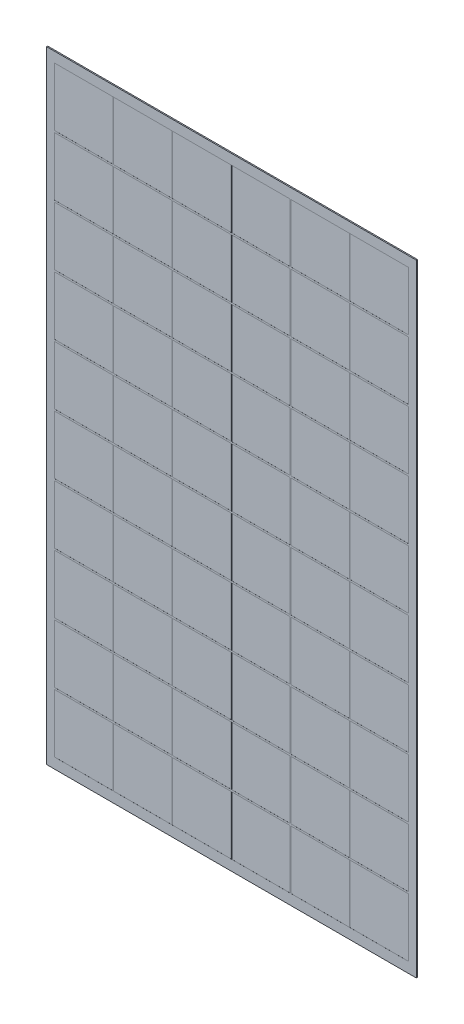
SolidWorks part; units mm, degrees
material "Glass"
ref_plane "Front Plane" through (0, 0, 0) normal (0, 0, 1) x (1, 0, 0)
ref_plane "Top Plane" through (0, 0, 0) normal (0, 1, 0) x (1, 0, 0)
ref_plane "Right Plane" through (0, 0, 0) normal (1, 0, 0) x (0, 0, -1)
sketch "Sketch1" plane through (0, 0, 0) normal (0, 0, 1) x (1, 0, 0)
  line L1 (0, 0) -> (980, 0)
  line L2 (0, 0) -> (0, 1648)
  line L3 (0, 1648) -> (980, 1648)
  line L4 (980, 0) -> (980, 1648)
  dimension "D1" = 980
  dimension "D2" = 1648
extrude "Boss-Extrude1" add sketch "Sketch1" along normal blind 3
sketch "Sketch2" plane through (0, 0, 3) normal (0, 0, 1) x (1, 0, 0)
  line L0 (0, 1648) -> (0, 0) construction
  line L1 (21, 1621) -> (176, 1621)
  line L2 (21, 1621) -> (21, 1466)
  line L3 (21, 1466) -> (176, 1466)
  line L4 (176, 1621) -> (176, 1466)
  line L5 (980, 1648) -> (0, 1648) construction
  line L6 (177.6, 1621) -> (177.6, 1466)
  line L7 (177.6, 1621) -> (332.6, 1621)
  line L8 (332.6, 1621) -> (332.6, 1466)
  line L9 (177.6, 1466) -> (332.6, 1466)
  line L10 (334.2, 1621) -> (334.2, 1466)
  line L11 (334.2, 1621) -> (489.2, 1621)
  line L12 (489.2, 1621) -> (489.2, 1466)
  line L13 (334.2, 1466) -> (489.2, 1466)
  line L14 (490.8, 1621) -> (490.8, 1466)
  line L15 (490.8, 1621) -> (645.8, 1621)
  line L16 (645.8, 1621) -> (645.8, 1466)
  line L17 (490.8, 1466) -> (645.8, 1466)
  line L18 (647.4, 1621) -> (647.4, 1466)
  line L19 (647.4, 1621) -> (802.4, 1621)
  line L20 (802.4, 1621) -> (802.4, 1466)
  line L21 (647.4, 1466) -> (802.4, 1466)
  line L22 (804, 1621) -> (804, 1466)
  line L23 (804, 1621) -> (959, 1621)
  line L24 (959, 1621) -> (959, 1466)
  line L25 (804, 1466) -> (959, 1466)
  line L27 (21, 1461.2) -> (21, 1306.2)
  line L28 (21, 1461.2) -> (176, 1461.2)
  line L29 (176, 1461.2) -> (176, 1306.2)
  line L30 (21, 1306.2) -> (176, 1306.2)
  line L31 (177.6, 1461.2) -> (177.6, 1306.2)
  line L32 (177.6, 1306.2) -> (332.6, 1306.2)
  line L33 (332.6, 1461.2) -> (332.6, 1306.2)
  line L34 (177.6, 1461.2) -> (332.6, 1461.2)
  line L35 (334.2, 1461.2) -> (334.2, 1306.2)
  line L36 (334.2, 1306.2) -> (489.2, 1306.2)
  line L37 (489.2, 1461.2) -> (489.2, 1306.2)
  line L38 (334.2, 1461.2) -> (489.2, 1461.2)
  line L39 (490.8, 1461.2) -> (490.8, 1306.2)
  line L40 (490.8, 1306.2) -> (645.8, 1306.2)
  line L41 (645.8, 1461.2) -> (645.8, 1306.2)
  line L42 (490.8, 1461.2) -> (645.8, 1461.2)
  line L43 (647.4, 1461.2) -> (647.4, 1306.2)
  line L44 (647.4, 1306.2) -> (802.4, 1306.2)
  line L45 (802.4, 1461.2) -> (802.4, 1306.2)
  line L46 (647.4, 1461.2) -> (802.4, 1461.2)
  line L47 (804, 1461.2) -> (804, 1306.2)
  line L48 (804, 1306.2) -> (959, 1306.2)
  line L49 (959, 1461.2) -> (959, 1306.2)
  line L50 (804, 1461.2) -> (959, 1461.2)
  line L51 (21, 1301.4) -> (21, 1146.4)
  line L52 (21, 1301.4) -> (176, 1301.4)
  line L53 (176, 1301.4) -> (176, 1146.4)
  line L54 (21, 1146.4) -> (176, 1146.4)
  line L55 (177.6, 1301.4) -> (177.6, 1146.4)
  line L56 (177.6, 1146.4) -> (332.6, 1146.4)
  line L57 (332.6, 1301.4) -> (332.6, 1146.4)
  line L58 (177.6, 1301.4) -> (332.6, 1301.4)
  line L59 (334.2, 1301.4) -> (334.2, 1146.4)
  line L60 (334.2, 1146.4) -> (489.2, 1146.4)
  line L61 (489.2, 1301.4) -> (489.2, 1146.4)
  line L62 (334.2, 1301.4) -> (489.2, 1301.4)
  line L63 (490.8, 1301.4) -> (490.8, 1146.4)
  line L64 (490.8, 1146.4) -> (645.8, 1146.4)
  line L65 (645.8, 1301.4) -> (645.8, 1146.4)
  line L66 (490.8, 1301.4) -> (645.8, 1301.4)
  line L67 (647.4, 1301.4) -> (647.4, 1146.4)
  line L68 (647.4, 1146.4) -> (802.4, 1146.4)
  line L69 (802.4, 1301.4) -> (802.4, 1146.4)
  line L70 (647.4, 1301.4) -> (802.4, 1301.4)
  line L71 (804, 1301.4) -> (804, 1146.4)
  line L72 (804, 1146.4) -> (959, 1146.4)
  line L73 (959, 1301.4) -> (959, 1146.4)
  line L74 (804, 1301.4) -> (959, 1301.4)
  line L75 (21, 1141.6) -> (21, 986.6)
  line L76 (21, 1141.6) -> (176, 1141.6)
  line L77 (176, 1141.6) -> (176, 986.6)
  line L78 (21, 986.6) -> (176, 986.6)
  line L79 (177.6, 1141.6) -> (177.6, 986.6)
  line L80 (177.6, 986.6) -> (332.6, 986.6)
  line L81 (332.6, 1141.6) -> (332.6, 986.6)
  line L82 (177.6, 1141.6) -> (332.6, 1141.6)
  line L83 (334.2, 1141.6) -> (334.2, 986.6)
  line L84 (334.2, 986.6) -> (489.2, 986.6)
  line L85 (489.2, 1141.6) -> (489.2, 986.6)
  line L86 (334.2, 1141.6) -> (489.2, 1141.6)
  line L87 (490.8, 1141.6) -> (490.8, 986.6)
  line L88 (490.8, 986.6) -> (645.8, 986.6)
  line L89 (645.8, 1141.6) -> (645.8, 986.6)
  line L90 (490.8, 1141.6) -> (645.8, 1141.6)
  line L91 (647.4, 1141.6) -> (647.4, 986.6)
  line L92 (647.4, 986.6) -> (802.4, 986.6)
  line L93 (802.4, 1141.6) -> (802.4, 986.6)
  line L94 (647.4, 1141.6) -> (802.4, 1141.6)
  line L95 (804, 1141.6) -> (804, 986.6)
  line L96 (804, 986.6) -> (959, 986.6)
  line L97 (959, 1141.6) -> (959, 986.6)
  line L98 (804, 1141.6) -> (959, 1141.6)
  line L99 (21, 981.8) -> (21, 826.8)
  line L100 (21, 981.8) -> (176, 981.8)
  line L101 (176, 981.8) -> (176, 826.8)
  line L102 (21, 826.8) -> (176, 826.8)
  line L103 (177.6, 981.8) -> (177.6, 826.8)
  line L104 (177.6, 826.8) -> (332.6, 826.8)
  line L105 (332.6, 981.8) -> (332.6, 826.8)
  line L106 (177.6, 981.8) -> (332.6, 981.8)
  line L107 (334.2, 981.8) -> (334.2, 826.8)
  line L108 (334.2, 826.8) -> (489.2, 826.8)
  line L109 (489.2, 981.8) -> (489.2, 826.8)
  line L110 (334.2, 981.8) -> (489.2, 981.8)
  line L111 (490.8, 981.8) -> (490.8, 826.8)
  line L112 (490.8, 826.8) -> (645.8, 826.8)
  line L113 (645.8, 981.8) -> (645.8, 826.8)
  line L114 (490.8, 981.8) -> (645.8, 981.8)
  line L115 (647.4, 981.8) -> (647.4, 826.8)
  line L116 (647.4, 826.8) -> (802.4, 826.8)
  line L117 (802.4, 981.8) -> (802.4, 826.8)
  line L118 (647.4, 981.8) -> (802.4, 981.8)
  line L119 (804, 981.8) -> (804, 826.8)
  line L120 (804, 826.8) -> (959, 826.8)
  line L121 (959, 981.8) -> (959, 826.8)
  line L122 (804, 981.8) -> (959, 981.8)
  line L123 (21, 822) -> (21, 667)
  line L124 (21, 822) -> (176, 822)
  line L125 (176, 822) -> (176, 667)
  line L126 (21, 667) -> (176, 667)
  line L127 (177.6, 822) -> (177.6, 667)
  line L128 (177.6, 667) -> (332.6, 667)
  line L129 (332.6, 822) -> (332.6, 667)
  line L130 (177.6, 822) -> (332.6, 822)
  line L131 (334.2, 822) -> (334.2, 667)
  line L132 (334.2, 667) -> (489.2, 667)
  line L133 (489.2, 822) -> (489.2, 667)
  line L134 (334.2, 822) -> (489.2, 822)
  line L135 (490.8, 822) -> (490.8, 667)
  line L136 (490.8, 667) -> (645.8, 667)
  line L137 (645.8, 822) -> (645.8, 667)
  line L138 (490.8, 822) -> (645.8, 822)
  line L139 (647.4, 822) -> (647.4, 667)
  line L140 (647.4, 667) -> (802.4, 667)
  line L141 (802.4, 822) -> (802.4, 667)
  line L142 (647.4, 822) -> (802.4, 822)
  line L143 (804, 822) -> (804, 667)
  line L144 (804, 667) -> (959, 667)
  line L145 (959, 822) -> (959, 667)
  line L146 (804, 822) -> (959, 822)
  line L147 (21, 662.2) -> (21, 507.2)
  line L148 (21, 662.2) -> (176, 662.2)
  line L149 (176, 662.2) -> (176, 507.2)
  line L150 (21, 507.2) -> (176, 507.2)
  line L151 (177.6, 662.2) -> (177.6, 507.2)
  line L152 (177.6, 507.2) -> (332.6, 507.2)
  line L153 (332.6, 662.2) -> (332.6, 507.2)
  line L154 (177.6, 662.2) -> (332.6, 662.2)
  line L155 (334.2, 662.2) -> (334.2, 507.2)
  line L156 (334.2, 507.2) -> (489.2, 507.2)
  line L157 (489.2, 662.2) -> (489.2, 507.2)
  line L158 (334.2, 662.2) -> (489.2, 662.2)
  line L159 (490.8, 662.2) -> (490.8, 507.2)
  line L160 (490.8, 507.2) -> (645.8, 507.2)
  line L161 (645.8, 662.2) -> (645.8, 507.2)
  line L162 (490.8, 662.2) -> (645.8, 662.2)
  line L163 (647.4, 662.2) -> (647.4, 507.2)
  line L164 (647.4, 507.2) -> (802.4, 507.2)
  line L165 (802.4, 662.2) -> (802.4, 507.2)
  line L166 (647.4, 662.2) -> (802.4, 662.2)
  line L167 (804, 662.2) -> (804, 507.2)
  line L168 (804, 507.2) -> (959, 507.2)
  line L169 (959, 662.2) -> (959, 507.2)
  line L170 (804, 662.2) -> (959, 662.2)
  line L171 (21, 502.4) -> (21, 347.4)
  line L172 (21, 502.4) -> (176, 502.4)
  line L173 (176, 502.4) -> (176, 347.4)
  line L174 (21, 347.4) -> (176, 347.4)
  line L175 (177.6, 502.4) -> (177.6, 347.4)
  line L176 (177.6, 347.4) -> (332.6, 347.4)
  line L177 (332.6, 502.4) -> (332.6, 347.4)
  line L178 (177.6, 502.4) -> (332.6, 502.4)
  line L179 (334.2, 502.4) -> (334.2, 347.4)
  line L180 (334.2, 347.4) -> (489.2, 347.4)
  line L181 (489.2, 502.4) -> (489.2, 347.4)
  line L182 (334.2, 502.4) -> (489.2, 502.4)
  line L183 (490.8, 502.4) -> (490.8, 347.4)
  line L184 (490.8, 347.4) -> (645.8, 347.4)
  line L185 (645.8, 502.4) -> (645.8, 347.4)
  line L186 (490.8, 502.4) -> (645.8, 502.4)
  line L187 (647.4, 502.4) -> (647.4, 347.4)
  line L188 (647.4, 347.4) -> (802.4, 347.4)
  line L189 (802.4, 502.4) -> (802.4, 347.4)
  line L190 (647.4, 502.4) -> (802.4, 502.4)
  line L191 (804, 502.4) -> (804, 347.4)
  line L192 (804, 347.4) -> (959, 347.4)
  line L193 (959, 502.4) -> (959, 347.4)
  line L194 (804, 502.4) -> (959, 502.4)
  line L195 (21, 342.6) -> (21, 187.6)
  line L196 (21, 342.6) -> (176, 342.6)
  line L197 (176, 342.6) -> (176, 187.6)
  line L198 (21, 187.6) -> (176, 187.6)
  line L199 (177.6, 342.6) -> (177.6, 187.6)
  line L200 (177.6, 187.6) -> (332.6, 187.6)
  line L201 (332.6, 342.6) -> (332.6, 187.6)
  line L202 (177.6, 342.6) -> (332.6, 342.6)
  line L203 (334.2, 342.6) -> (334.2, 187.6)
  line L204 (334.2, 187.6) -> (489.2, 187.6)
  line L205 (489.2, 342.6) -> (489.2, 187.6)
  line L206 (334.2, 342.6) -> (489.2, 342.6)
  line L207 (490.8, 342.6) -> (490.8, 187.6)
  line L208 (490.8, 187.6) -> (645.8, 187.6)
  line L209 (645.8, 342.6) -> (645.8, 187.6)
  line L210 (490.8, 342.6) -> (645.8, 342.6)
  line L211 (647.4, 342.6) -> (647.4, 187.6)
  line L212 (647.4, 187.6) -> (802.4, 187.6)
  line L213 (802.4, 342.6) -> (802.4, 187.6)
  line L214 (647.4, 342.6) -> (802.4, 342.6)
  line L215 (804, 342.6) -> (804, 187.6)
  line L216 (804, 187.6) -> (959, 187.6)
  line L217 (959, 342.6) -> (959, 187.6)
  line L218 (804, 342.6) -> (959, 342.6)
  line L219 (21, 182.8) -> (21, 27.8)
  line L220 (21, 182.8) -> (176, 182.8)
  line L221 (176, 182.8) -> (176, 27.8)
  line L222 (21, 27.8) -> (176, 27.8)
  line L223 (177.6, 182.8) -> (177.6, 27.8)
  line L224 (177.6, 27.8) -> (332.6, 27.8)
  line L225 (332.6, 182.8) -> (332.6, 27.8)
  line L226 (177.6, 182.8) -> (332.6, 182.8)
  line L227 (334.2, 182.8) -> (334.2, 27.8)
  line L228 (334.2, 27.8) -> (489.2, 27.8)
  line L229 (489.2, 182.8) -> (489.2, 27.8)
  line L230 (334.2, 182.8) -> (489.2, 182.8)
  line L231 (490.8, 182.8) -> (490.8, 27.8)
  line L232 (490.8, 27.8) -> (645.8, 27.8)
  line L233 (645.8, 182.8) -> (645.8, 27.8)
  line L234 (490.8, 182.8) -> (645.8, 182.8)
  line L235 (647.4, 182.8) -> (647.4, 27.8)
  line L236 (647.4, 27.8) -> (802.4, 27.8)
  line L237 (802.4, 182.8) -> (802.4, 27.8)
  line L238 (647.4, 182.8) -> (802.4, 182.8)
  line L239 (804, 182.8) -> (804, 27.8)
  line L240 (804, 27.8) -> (959, 27.8)
  line L241 (959, 182.8) -> (959, 27.8)
  line L242 (804, 182.8) -> (959, 182.8)
  dimension "D1" = 155
  dimension "D2" = 155
  dimension "D3" = 21
  dimension "D4" = 27
  dimension "D6" = 1.6
  dimension "D7" = 10
  dimension "D8" = 4.8
  dimension "D5" = 6
extrude "Cut-Extrude1" cut sketch "Sketch2" against normal blind 0.1
sketch "Sketch3" plane through (0, 0, 0) normal (0, 0, -1) x (-1, 0, 0)
  line L0 (-980, 1648) -> (0, 1648) construction
  line L1 (-141, 1617) -> (-66, 1617)
  line L2 (-141, 1617) -> (-141, 1612)
  line L3 (-141, 1612) -> (-66, 1612)
  line L4 (-66, 1617) -> (-66, 1612)
  line L5 (0, 1648) -> (0, 0) construction
  line L6 (-141, 1457) -> (-66, 1457)
  line L7 (-141, 1472) -> (-66, 1472)
  line L8 (-141, 1472) -> (-141, 1467)
  line L9 (-141, 1467) -> (-66, 1467)
  line L10 (-66, 1472) -> (-66, 1467)
  line L11 (-141, 1457) -> (-141, 1452)
  line L12 (-66, 1457) -> (-66, 1452)
  line L13 (-141, 1452) -> (-66, 1452)
  line L14 (-141, 1312) -> (-141, 1307)
  line L15 (-141, 1312) -> (-66, 1312)
  line L16 (-66, 1312) -> (-66, 1307)
  line L17 (-141, 1307) -> (-66, 1307)
  line L18 (-141, 1297) -> (-66, 1297)
  line L19 (-141, 1297) -> (-141, 1292)
  line L20 (-66, 1297) -> (-66, 1292)
  line L21 (-141, 1292) -> (-66, 1292)
  line L22 (-141, 1152) -> (-141, 1147)
  line L23 (-141, 1152) -> (-66, 1152)
  line L24 (-66, 1152) -> (-66, 1147)
  line L25 (-141, 1147) -> (-66, 1147)
  line L26 (-141, 1137) -> (-66, 1137)
  line L27 (-141, 1137) -> (-141, 1132)
  line L28 (-66, 1137) -> (-66, 1132)
  line L29 (-141, 1132) -> (-66, 1132)
  line L30 (-141, 992) -> (-141, 987)
  line L31 (-141, 992) -> (-66, 992)
  line L32 (-66, 992) -> (-66, 987)
  line L33 (-141, 987) -> (-66, 987)
  line L34 (-141, 977) -> (-66, 977)
  line L35 (-141, 977) -> (-141, 972)
  line L36 (-66, 977) -> (-66, 972)
  line L37 (-141, 972) -> (-66, 972)
  line L38 (-141, 832) -> (-141, 827)
  line L39 (-141, 832) -> (-66, 832)
  line L40 (-66, 832) -> (-66, 827)
  line L41 (-141, 827) -> (-66, 827)
  line L42 (-141, 817) -> (-66, 817)
  line L43 (-141, 817) -> (-141, 812)
  line L44 (-66, 817) -> (-66, 812)
  line L45 (-141, 812) -> (-66, 812)
  line L46 (-141, 672) -> (-141, 667)
  line L47 (-141, 672) -> (-66, 672)
  line L48 (-66, 672) -> (-66, 667)
  line L49 (-141, 667) -> (-66, 667)
  line L50 (-141, 657) -> (-66, 657)
  line L51 (-141, 657) -> (-141, 652)
  line L52 (-66, 657) -> (-66, 652)
  line L53 (-141, 652) -> (-66, 652)
  line L54 (-141, 512) -> (-141, 507)
  line L55 (-141, 512) -> (-66, 512)
  line L56 (-66, 512) -> (-66, 507)
  line L57 (-141, 507) -> (-66, 507)
  line L58 (-141, 497) -> (-66, 497)
  line L59 (-141, 497) -> (-141, 492)
  line L60 (-66, 497) -> (-66, 492)
  line L61 (-141, 492) -> (-66, 492)
  line L62 (-141, 352) -> (-141, 347)
  line L63 (-141, 352) -> (-66, 352)
  line L64 (-66, 352) -> (-66, 347)
  line L65 (-141, 347) -> (-66, 347)
  line L66 (-141, 337) -> (-66, 337)
  line L67 (-141, 337) -> (-141, 332)
  line L68 (-66, 337) -> (-66, 332)
  line L69 (-141, 332) -> (-66, 332)
  line L70 (-141, 192) -> (-141, 187)
  line L71 (-141, 192) -> (-66, 192)
  line L72 (-66, 192) -> (-66, 187)
  line L73 (-141, 187) -> (-66, 187)
  line L74 (-141, 177) -> (-66, 177)
  line L75 (-141, 177) -> (-141, 172)
  line L76 (-66, 177) -> (-66, 172)
  line L77 (-141, 172) -> (-66, 172)
  line L78 (-141, 32) -> (-141, 27)
  line L79 (-141, 32) -> (-66, 32)
  line L80 (-66, 32) -> (-66, 27)
  line L81 (-141, 27) -> (-66, 27)
  line L82 (-296, 1617) -> (-296, 1612)
  line L83 (-296, 1617) -> (-221, 1617)
  line L84 (-221, 1617) -> (-221, 1612)
  line L85 (-296, 1612) -> (-221, 1612)
  line L86 (-296, 1472) -> (-296, 1467)
  line L87 (-296, 1472) -> (-221, 1472)
  line L88 (-221, 1472) -> (-221, 1467)
  line L89 (-296, 1467) -> (-221, 1467)
  line L90 (-296, 1457) -> (-221, 1457)
  line L91 (-221, 1457) -> (-221, 1452)
  line L92 (-296, 1452) -> (-221, 1452)
  line L93 (-296, 1457) -> (-296, 1452)
  line L94 (-296, 1312) -> (-296, 1307)
  line L95 (-296, 1307) -> (-221, 1307)
  line L96 (-221, 1312) -> (-221, 1307)
  line L97 (-296, 1312) -> (-221, 1312)
  line L98 (-296, 1297) -> (-221, 1297)
  line L99 (-221, 1297) -> (-221, 1292)
  line L100 (-296, 1292) -> (-221, 1292)
  line L101 (-296, 1297) -> (-296, 1292)
  line L102 (-296, 1152) -> (-296, 1147)
  line L103 (-296, 1147) -> (-221, 1147)
  line L104 (-221, 1152) -> (-221, 1147)
  line L105 (-296, 1152) -> (-221, 1152)
  line L106 (-296, 1137) -> (-221, 1137)
  line L107 (-221, 1137) -> (-221, 1132)
  line L108 (-296, 1132) -> (-221, 1132)
  line L109 (-296, 1137) -> (-296, 1132)
  line L110 (-296, 992) -> (-296, 987)
  line L111 (-296, 987) -> (-221, 987)
  line L112 (-221, 992) -> (-221, 987)
  line L113 (-296, 992) -> (-221, 992)
  line L114 (-296, 977) -> (-221, 977)
  line L115 (-221, 977) -> (-221, 972)
  line L116 (-296, 972) -> (-221, 972)
  line L117 (-296, 977) -> (-296, 972)
  line L118 (-296, 832) -> (-296, 827)
  line L119 (-296, 827) -> (-221, 827)
  line L120 (-221, 832) -> (-221, 827)
  line L121 (-296, 832) -> (-221, 832)
  line L122 (-296, 817) -> (-221, 817)
  line L123 (-221, 817) -> (-221, 812)
  line L124 (-296, 812) -> (-221, 812)
  line L125 (-296, 817) -> (-296, 812)
  line L126 (-296, 672) -> (-296, 667)
  line L127 (-296, 667) -> (-221, 667)
  line L128 (-221, 672) -> (-221, 667)
  line L129 (-296, 672) -> (-221, 672)
  line L130 (-296, 657) -> (-221, 657)
  line L131 (-221, 657) -> (-221, 652)
  line L132 (-296, 652) -> (-221, 652)
  line L133 (-296, 657) -> (-296, 652)
  line L134 (-296, 512) -> (-296, 507)
  line L135 (-296, 507) -> (-221, 507)
  line L136 (-221, 512) -> (-221, 507)
  line L137 (-296, 512) -> (-221, 512)
  line L138 (-296, 497) -> (-221, 497)
  line L139 (-221, 497) -> (-221, 492)
  line L140 (-296, 492) -> (-221, 492)
  line L141 (-296, 497) -> (-296, 492)
  line L142 (-296, 352) -> (-296, 347)
  line L143 (-296, 347) -> (-221, 347)
  line L144 (-221, 352) -> (-221, 347)
  line L145 (-296, 352) -> (-221, 352)
  line L146 (-296, 337) -> (-221, 337)
  line L147 (-221, 337) -> (-221, 332)
  line L148 (-296, 332) -> (-221, 332)
  line L149 (-296, 337) -> (-296, 332)
  line L150 (-296, 192) -> (-296, 187)
  line L151 (-296, 187) -> (-221, 187)
  line L152 (-221, 192) -> (-221, 187)
  line L153 (-296, 192) -> (-221, 192)
  line L154 (-296, 177) -> (-221, 177)
  line L155 (-221, 177) -> (-221, 172)
  line L156 (-296, 172) -> (-221, 172)
  line L157 (-296, 177) -> (-296, 172)
  line L158 (-296, 32) -> (-296, 27)
  line L159 (-296, 27) -> (-221, 27)
  line L160 (-221, 32) -> (-221, 27)
  line L161 (-296, 32) -> (-221, 32)
  line L162 (-451, 1617) -> (-451, 1612)
  line L163 (-451, 1617) -> (-376, 1617)
  line L164 (-376, 1617) -> (-376, 1612)
  line L165 (-451, 1612) -> (-376, 1612)
  line L166 (-451, 1472) -> (-451, 1467)
  line L167 (-451, 1472) -> (-376, 1472)
  line L168 (-376, 1472) -> (-376, 1467)
  line L169 (-451, 1467) -> (-376, 1467)
  line L170 (-451, 1457) -> (-376, 1457)
  line L171 (-376, 1457) -> (-376, 1452)
  line L172 (-451, 1452) -> (-376, 1452)
  line L173 (-451, 1457) -> (-451, 1452)
  line L174 (-451, 1312) -> (-451, 1307)
  line L175 (-451, 1307) -> (-376, 1307)
  line L176 (-376, 1312) -> (-376, 1307)
  line L177 (-451, 1312) -> (-376, 1312)
  line L178 (-451, 1297) -> (-376, 1297)
  line L179 (-376, 1297) -> (-376, 1292)
  line L180 (-451, 1292) -> (-376, 1292)
  line L181 (-451, 1297) -> (-451, 1292)
  line L182 (-451, 1152) -> (-451, 1147)
  line L183 (-451, 1147) -> (-376, 1147)
  line L184 (-376, 1152) -> (-376, 1147)
  line L185 (-451, 1152) -> (-376, 1152)
  line L186 (-451, 1137) -> (-376, 1137)
  line L187 (-376, 1137) -> (-376, 1132)
  line L188 (-451, 1132) -> (-376, 1132)
  line L189 (-451, 1137) -> (-451, 1132)
  line L190 (-451, 992) -> (-451, 987)
  line L191 (-451, 987) -> (-376, 987)
  line L192 (-376, 992) -> (-376, 987)
  line L193 (-451, 992) -> (-376, 992)
  line L194 (-451, 977) -> (-376, 977)
  line L195 (-376, 977) -> (-376, 972)
  line L196 (-451, 972) -> (-376, 972)
  line L197 (-451, 977) -> (-451, 972)
  line L198 (-451, 832) -> (-451, 827)
  line L199 (-451, 827) -> (-376, 827)
  line L200 (-376, 832) -> (-376, 827)
  line L201 (-451, 832) -> (-376, 832)
  line L202 (-451, 817) -> (-376, 817)
  line L203 (-376, 817) -> (-376, 812)
  line L204 (-451, 812) -> (-376, 812)
  line L205 (-451, 817) -> (-451, 812)
  line L206 (-451, 672) -> (-451, 667)
  line L207 (-451, 667) -> (-376, 667)
  line L208 (-376, 672) -> (-376, 667)
  line L209 (-451, 672) -> (-376, 672)
  line L210 (-451, 657) -> (-376, 657)
  line L211 (-376, 657) -> (-376, 652)
  line L212 (-451, 652) -> (-376, 652)
  line L213 (-451, 657) -> (-451, 652)
  line L214 (-451, 512) -> (-451, 507)
  line L215 (-451, 507) -> (-376, 507)
  line L216 (-376, 512) -> (-376, 507)
  line L217 (-451, 512) -> (-376, 512)
  line L218 (-451, 497) -> (-376, 497)
  line L219 (-376, 497) -> (-376, 492)
  line L220 (-451, 492) -> (-376, 492)
  line L221 (-451, 497) -> (-451, 492)
  line L222 (-451, 352) -> (-451, 347)
  line L223 (-451, 347) -> (-376, 347)
  line L224 (-376, 352) -> (-376, 347)
  line L225 (-451, 352) -> (-376, 352)
  line L226 (-451, 337) -> (-376, 337)
  line L227 (-376, 337) -> (-376, 332)
  line L228 (-451, 332) -> (-376, 332)
  line L229 (-451, 337) -> (-451, 332)
  line L230 (-451, 192) -> (-451, 187)
  line L231 (-451, 187) -> (-376, 187)
  line L232 (-376, 192) -> (-376, 187)
  line L233 (-451, 192) -> (-376, 192)
  line L234 (-451, 177) -> (-376, 177)
  line L235 (-376, 177) -> (-376, 172)
  line L236 (-451, 172) -> (-376, 172)
  line L237 (-451, 177) -> (-451, 172)
  line L238 (-451, 32) -> (-451, 27)
  line L239 (-451, 27) -> (-376, 27)
  line L240 (-376, 32) -> (-376, 27)
  line L241 (-451, 32) -> (-376, 32)
  line L242 (-606, 1617) -> (-606, 1612)
  line L243 (-606, 1617) -> (-531, 1617)
  line L244 (-531, 1617) -> (-531, 1612)
  line L245 (-606, 1612) -> (-531, 1612)
  line L246 (-606, 1472) -> (-606, 1467)
  line L247 (-606, 1472) -> (-531, 1472)
  line L248 (-531, 1472) -> (-531, 1467)
  line L249 (-606, 1467) -> (-531, 1467)
  line L250 (-606, 1457) -> (-531, 1457)
  line L251 (-531, 1457) -> (-531, 1452)
  line L252 (-606, 1452) -> (-531, 1452)
  line L253 (-606, 1457) -> (-606, 1452)
  line L254 (-606, 1312) -> (-606, 1307)
  line L255 (-606, 1307) -> (-531, 1307)
  line L256 (-531, 1312) -> (-531, 1307)
  line L257 (-606, 1312) -> (-531, 1312)
  line L258 (-606, 1297) -> (-531, 1297)
  line L259 (-531, 1297) -> (-531, 1292)
  line L260 (-606, 1292) -> (-531, 1292)
  line L261 (-606, 1297) -> (-606, 1292)
  line L262 (-606, 1152) -> (-606, 1147)
  line L263 (-606, 1147) -> (-531, 1147)
  line L264 (-531, 1152) -> (-531, 1147)
  line L265 (-606, 1152) -> (-531, 1152)
  line L266 (-606, 1137) -> (-531, 1137)
  line L267 (-531, 1137) -> (-531, 1132)
  line L268 (-606, 1132) -> (-531, 1132)
  line L269 (-606, 1137) -> (-606, 1132)
  line L270 (-606, 992) -> (-606, 987)
  line L271 (-606, 987) -> (-531, 987)
  line L272 (-531, 992) -> (-531, 987)
  line L273 (-606, 992) -> (-531, 992)
  line L274 (-606, 977) -> (-531, 977)
  line L275 (-531, 977) -> (-531, 972)
  line L276 (-606, 972) -> (-531, 972)
  line L277 (-606, 977) -> (-606, 972)
  line L278 (-606, 832) -> (-606, 827)
  line L279 (-606, 827) -> (-531, 827)
  line L280 (-531, 832) -> (-531, 827)
  line L281 (-606, 832) -> (-531, 832)
  line L282 (-606, 817) -> (-531, 817)
  line L283 (-531, 817) -> (-531, 812)
  line L284 (-606, 812) -> (-531, 812)
  line L285 (-606, 817) -> (-606, 812)
  line L286 (-606, 672) -> (-606, 667)
  line L287 (-606, 667) -> (-531, 667)
  line L288 (-531, 672) -> (-531, 667)
  line L289 (-606, 672) -> (-531, 672)
  line L290 (-606, 657) -> (-531, 657)
  line L291 (-531, 657) -> (-531, 652)
  line L292 (-606, 652) -> (-531, 652)
  line L293 (-606, 657) -> (-606, 652)
  line L294 (-606, 512) -> (-606, 507)
  line L295 (-606, 507) -> (-531, 507)
  line L296 (-531, 512) -> (-531, 507)
  line L297 (-606, 512) -> (-531, 512)
  line L298 (-606, 497) -> (-531, 497)
  line L299 (-531, 497) -> (-531, 492)
  line L300 (-606, 492) -> (-531, 492)
  line L301 (-606, 497) -> (-606, 492)
  line L302 (-606, 352) -> (-606, 347)
  line L303 (-606, 347) -> (-531, 347)
  line L304 (-531, 352) -> (-531, 347)
  line L305 (-606, 352) -> (-531, 352)
  line L306 (-606, 337) -> (-531, 337)
  line L307 (-531, 337) -> (-531, 332)
  line L308 (-606, 332) -> (-531, 332)
  line L309 (-606, 337) -> (-606, 332)
  line L310 (-606, 192) -> (-606, 187)
  line L311 (-606, 187) -> (-531, 187)
  line L312 (-531, 192) -> (-531, 187)
  line L313 (-606, 192) -> (-531, 192)
  line L314 (-606, 177) -> (-531, 177)
  line L315 (-531, 177) -> (-531, 172)
  line L316 (-606, 172) -> (-531, 172)
  line L317 (-606, 177) -> (-606, 172)
  line L318 (-606, 32) -> (-606, 27)
  line L319 (-606, 27) -> (-531, 27)
  line L320 (-531, 32) -> (-531, 27)
  line L321 (-606, 32) -> (-531, 32)
  line L322 (-761, 1617) -> (-761, 1612)
  line L323 (-761, 1617) -> (-686, 1617)
  line L324 (-686, 1617) -> (-686, 1612)
  line L325 (-761, 1612) -> (-686, 1612)
  line L326 (-761, 1472) -> (-761, 1467)
  line L327 (-761, 1472) -> (-686, 1472)
  line L328 (-686, 1472) -> (-686, 1467)
  line L329 (-761, 1467) -> (-686, 1467)
  line L330 (-761, 1457) -> (-686, 1457)
  line L331 (-686, 1457) -> (-686, 1452)
  line L332 (-761, 1452) -> (-686, 1452)
  line L333 (-761, 1457) -> (-761, 1452)
  line L334 (-761, 1312) -> (-761, 1307)
  line L335 (-761, 1307) -> (-686, 1307)
  line L336 (-686, 1312) -> (-686, 1307)
  line L337 (-761, 1312) -> (-686, 1312)
  line L338 (-761, 1297) -> (-686, 1297)
  line L339 (-686, 1297) -> (-686, 1292)
  line L340 (-761, 1292) -> (-686, 1292)
  line L341 (-761, 1297) -> (-761, 1292)
  line L342 (-761, 1152) -> (-761, 1147)
  line L343 (-761, 1147) -> (-686, 1147)
  line L344 (-686, 1152) -> (-686, 1147)
  line L345 (-761, 1152) -> (-686, 1152)
  line L346 (-761, 1137) -> (-686, 1137)
  line L347 (-686, 1137) -> (-686, 1132)
  line L348 (-761, 1132) -> (-686, 1132)
  line L349 (-761, 1137) -> (-761, 1132)
  line L350 (-761, 992) -> (-761, 987)
  line L351 (-761, 987) -> (-686, 987)
  line L352 (-686, 992) -> (-686, 987)
  line L353 (-761, 992) -> (-686, 992)
  line L354 (-761, 977) -> (-686, 977)
  line L355 (-686, 977) -> (-686, 972)
  line L356 (-761, 972) -> (-686, 972)
  line L357 (-761, 977) -> (-761, 972)
  line L358 (-761, 832) -> (-761, 827)
  line L359 (-761, 827) -> (-686, 827)
  line L360 (-686, 832) -> (-686, 827)
  line L361 (-761, 832) -> (-686, 832)
  line L362 (-761, 817) -> (-686, 817)
  line L363 (-686, 817) -> (-686, 812)
  line L364 (-761, 812) -> (-686, 812)
  line L365 (-761, 817) -> (-761, 812)
  line L366 (-761, 672) -> (-761, 667)
  line L367 (-761, 667) -> (-686, 667)
  line L368 (-686, 672) -> (-686, 667)
  line L369 (-761, 672) -> (-686, 672)
  line L370 (-761, 657) -> (-686, 657)
  line L371 (-686, 657) -> (-686, 652)
  line L372 (-761, 652) -> (-686, 652)
  line L373 (-761, 657) -> (-761, 652)
  line L374 (-761, 512) -> (-761, 507)
  line L375 (-761, 507) -> (-686, 507)
  line L376 (-686, 512) -> (-686, 507)
  line L377 (-761, 512) -> (-686, 512)
  line L378 (-761, 497) -> (-686, 497)
  line L379 (-686, 497) -> (-686, 492)
  line L380 (-761, 492) -> (-686, 492)
  line L381 (-761, 497) -> (-761, 492)
  line L382 (-761, 352) -> (-761, 347)
  line L383 (-761, 347) -> (-686, 347)
  line L384 (-686, 352) -> (-686, 347)
  line L385 (-761, 352) -> (-686, 352)
  line L386 (-761, 337) -> (-686, 337)
  line L387 (-686, 337) -> (-686, 332)
  line L388 (-761, 332) -> (-686, 332)
  line L389 (-761, 337) -> (-761, 332)
  line L390 (-761, 192) -> (-761, 187)
  line L391 (-761, 187) -> (-686, 187)
  line L392 (-686, 192) -> (-686, 187)
  line L393 (-761, 192) -> (-686, 192)
  line L394 (-761, 177) -> (-686, 177)
  line L395 (-686, 177) -> (-686, 172)
  line L396 (-761, 172) -> (-686, 172)
  line L397 (-761, 177) -> (-761, 172)
  line L398 (-761, 32) -> (-761, 27)
  line L399 (-761, 27) -> (-686, 27)
  line L400 (-686, 32) -> (-686, 27)
  line L401 (-761, 32) -> (-686, 32)
  line L402 (-916, 1617) -> (-916, 1612)
  line L403 (-916, 1617) -> (-841, 1617)
  line L404 (-841, 1617) -> (-841, 1612)
  line L405 (-916, 1612) -> (-841, 1612)
  line L406 (-916, 1472) -> (-916, 1467)
  line L407 (-916, 1472) -> (-841, 1472)
  line L408 (-841, 1472) -> (-841, 1467)
  line L409 (-916, 1467) -> (-841, 1467)
  line L410 (-916, 1457) -> (-841, 1457)
  line L411 (-841, 1457) -> (-841, 1452)
  line L412 (-916, 1452) -> (-841, 1452)
  line L413 (-916, 1457) -> (-916, 1452)
  line L414 (-916, 1312) -> (-916, 1307)
  line L415 (-916, 1307) -> (-841, 1307)
  line L416 (-841, 1312) -> (-841, 1307)
  line L417 (-916, 1312) -> (-841, 1312)
  line L418 (-916, 1297) -> (-841, 1297)
  line L419 (-841, 1297) -> (-841, 1292)
  line L420 (-916, 1292) -> (-841, 1292)
  line L421 (-916, 1297) -> (-916, 1292)
  line L422 (-916, 1152) -> (-916, 1147)
  line L423 (-916, 1147) -> (-841, 1147)
  line L424 (-841, 1152) -> (-841, 1147)
  line L425 (-916, 1152) -> (-841, 1152)
  line L426 (-916, 1137) -> (-841, 1137)
  line L427 (-841, 1137) -> (-841, 1132)
  line L428 (-916, 1132) -> (-841, 1132)
  line L429 (-916, 1137) -> (-916, 1132)
  line L430 (-916, 992) -> (-916, 987)
  line L431 (-916, 987) -> (-841, 987)
  line L432 (-841, 992) -> (-841, 987)
  line L433 (-916, 992) -> (-841, 992)
  line L434 (-916, 977) -> (-841, 977)
  line L435 (-841, 977) -> (-841, 972)
  line L436 (-916, 972) -> (-841, 972)
  line L437 (-916, 977) -> (-916, 972)
  line L438 (-916, 832) -> (-916, 827)
  line L439 (-916, 827) -> (-841, 827)
  line L440 (-841, 832) -> (-841, 827)
  line L441 (-916, 832) -> (-841, 832)
  line L442 (-916, 817) -> (-841, 817)
  line L443 (-841, 817) -> (-841, 812)
  line L444 (-916, 812) -> (-841, 812)
  line L445 (-916, 817) -> (-916, 812)
  line L446 (-916, 672) -> (-916, 667)
  line L447 (-916, 667) -> (-841, 667)
  line L448 (-841, 672) -> (-841, 667)
  line L449 (-916, 672) -> (-841, 672)
  line L450 (-916, 657) -> (-841, 657)
  line L451 (-841, 657) -> (-841, 652)
  line L452 (-916, 652) -> (-841, 652)
  line L453 (-916, 657) -> (-916, 652)
  line L454 (-916, 512) -> (-916, 507)
  line L455 (-916, 507) -> (-841, 507)
  line L456 (-841, 512) -> (-841, 507)
  line L457 (-916, 512) -> (-841, 512)
  line L458 (-916, 497) -> (-841, 497)
  line L459 (-841, 497) -> (-841, 492)
  line L460 (-916, 492) -> (-841, 492)
  line L461 (-916, 497) -> (-916, 492)
  line L462 (-916, 352) -> (-916, 347)
  line L463 (-916, 347) -> (-841, 347)
  line L464 (-841, 352) -> (-841, 347)
  line L465 (-916, 352) -> (-841, 352)
  line L466 (-916, 337) -> (-841, 337)
  line L467 (-841, 337) -> (-841, 332)
  line L468 (-916, 332) -> (-841, 332)
  line L469 (-916, 337) -> (-916, 332)
  line L470 (-916, 192) -> (-916, 187)
  line L471 (-916, 187) -> (-841, 187)
  line L472 (-841, 192) -> (-841, 187)
  line L473 (-916, 192) -> (-841, 192)
  line L474 (-916, 177) -> (-841, 177)
  line L475 (-841, 177) -> (-841, 172)
  line L476 (-916, 172) -> (-841, 172)
  line L477 (-916, 177) -> (-916, 172)
  line L478 (-916, 32) -> (-916, 27)
  line L479 (-916, 27) -> (-841, 27)
  line L480 (-841, 32) -> (-841, 27)
  line L481 (-916, 32) -> (-841, 32)
  dimension "D1" = 75
  dimension "D2" = 5
  dimension "D3" = 31
  dimension "D4" = 66
  dimension "D5" = 140
  dimension "D6" = 5
  dimension "D7" = 75
  dimension "D8" = 66
  dimension "D10" = 10
  dimension "D12" = 80
  dimension "D9" = 10
  dimension "D11" = 6
extrude "Boss-Extrude2" add sketch "Sketch3" along normal blind 0.5
